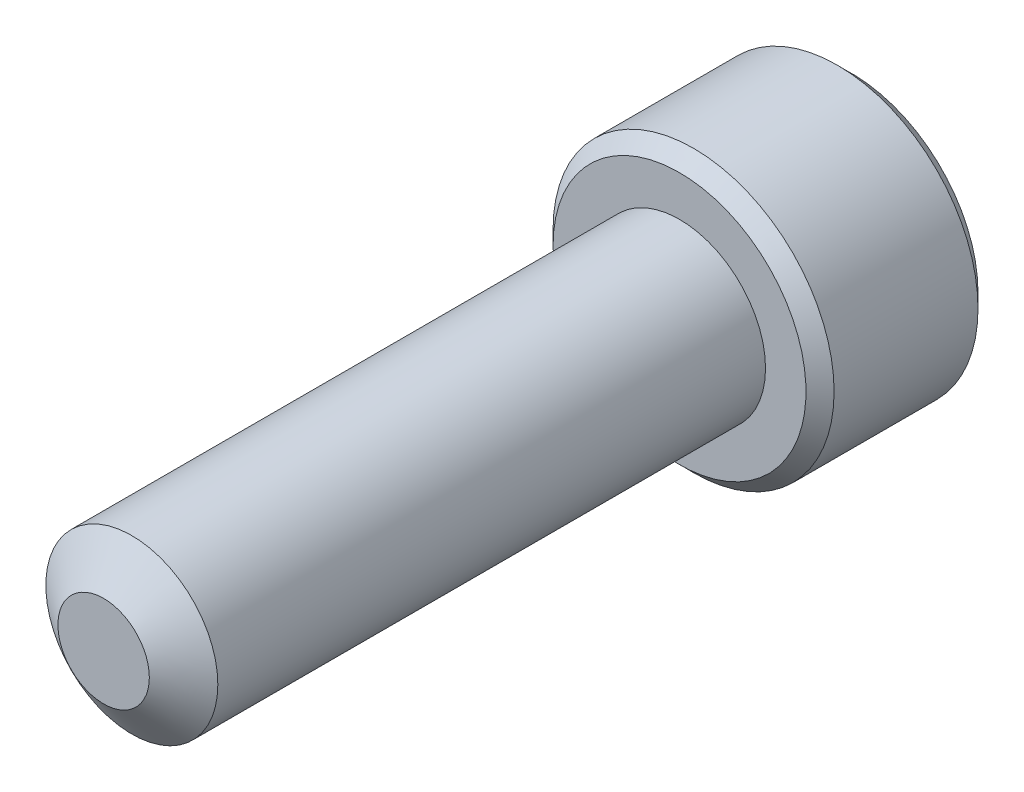
SolidWorks part; units mm, degrees
material "6061 Alloy"
ref_plane "Front Plane" through (0, 0, 0) normal (0, 0, 1) x (1, 0, 0)
ref_plane "Top Plane" through (0, 0, 0) normal (0, 1, 0) x (1, 0, 0)
ref_plane "Right Plane" through (0, 0, 0) normal (1, 0, 0) x (0, 0, -1)
sketch "Sketch1" plane through (0, 0, 0) normal (0, 0, 1) x (1, 0, 0)
  circle A0 centre (0, 0) radius 1.4224
  dimension "OD" = 2.8448
extrude "Extrude1" add sketch "Sketch1" against normal blind 9.525
sketch "Sketch2" plane through (0, 0, 0) normal (0, 0, 1) x (1, 0, 0)
  circle A0 centre (0, 0) radius 1.4224 construction
  circle A1 centre (0, 0) radius 1.4224
curve "Helix/Spiral1" [suppressed] pitch 0.635 height 10.16 turns 16 parameters "pitch"=0.635
sketch "Sketch3" plane through (0, 0, 0) normal (1, 0, 0) x (0, 0, -1)
  line L0 (-0.5556, 1.4224) -> (-0.3175, 1.01)
  line L1 (-0.3175, 1.01) -> (-0.2381, 1.01)
  line L2 (-0.2381, 1.01) -> (0, 1.4224)
  line L3 (-0.5556, 1.4224) -> (0, 1.4224)
  line L4 (-0.2778, 1.4224) -> (-0.2778, 1.01) construction
  line L5 (-0.4366, 1.2162) -> (-0.1191, 1.2162) construction
  line L6 (0, 1.4224) -> (0, -1.4224) construction
  dimension "D1" = 0.0794
  dimension "D2" = 0.3175
  dimension "D3" = 60
sweep "Cut-Sweep1" [suppressed] cut profiles "Sketch3" path "Helix/Spiral1"
sketch "Sketch4" plane through (0, 0, 0) normal (1, 0, 0) x (0, 0, -1)
  line L0 (0.4666, 1.4224) -> (0, 0.756)
  line L1 (0, 0.756) -> (0, 1.4224)
  line L2 (0.4666, 1.4224) -> (0, 1.4224)
  line L3 (-0.5556, 1.4224) -> (0, 1.4224) construction
  line L4 (0, 0) -> (7.0209, 0) construction
  dimension "D1" = 55
  dimension "D2" = 0.254
revolve "Cut-Revolve1" cut sketch "Sketch4" angle 360 about L4
sketch "Sketch6" plane through (0, 0, -9.525) normal (0, 0, -1) x (-1, 0, 0)
  circle A0 centre (0, 0) radius 2.3241
  dimension "head dia" = 4.6482
extrude "Extrude2" add sketch "Sketch6" along normal blind 2.8448
sketch "Sketch7" plane through (0, 0, -12.3698) normal (0, 0, -1) x (-1, 0, 0)
  line L1 (0, 1.3748) -> (-1.1906, 0.6874)
  line L2 (-1.1906, 0.6874) -> (-1.1906, -0.6874)
  line L3 (-1.1906, -0.6874) -> (0, -1.3748)
  line L4 (0, -1.3748) -> (1.1906, -0.6874)
  line L5 (1.1906, -0.6874) -> (1.1906, 0.6874)
  line L6 (1.1906, 0.6874) -> (0, 1.3748)
  circle A0 centre (0, 0) radius 1.1906 construction
  dimension "hex dia" = 2.3813
extrude "Cut-Extrude1" cut sketch "Sketch7" against normal blind 1.7859
sketch "Sketch8" plane through (0, 0, -12.3698) normal (0, 0, -1) x (-1, 0, 0)
  circle A0 centre (0, 0) radius 1.3748
extrude "Cut-Extrude2" cut sketch "Sketch8" against normal through all draft 45
chamfer "Chamfer1" distance 0.2324 angle 45 2 edges at (-2.3241, 0, -12.3698) (-2.3241, 0, -9.525)
sketch "Sketch10" plane through (0, 0, -9.525) normal (0, 0, 1) x (1, 0, 0)
  circle A1 centre (0, 0) radius 1.4224
  circle A2 centre (0, 0) radius 1.4224
  dimension "D1" = 0
ref_plane "Plane1" through (0, 0, 0) normal (0, 0, 1) x (1, 0, 0)
extrude "partial thread" [suppressed] add sketch "Sketch10" along normal up to surface (12.7 mm away) separate body up to plane "Plane1"
chamfer "Chamfer2" [suppressed] distance 0.0569 angle 45
combine bodies "Combine1" [suppressed] operation type add bodies to combine 107 108
sketch "Sketch9" [suppressed] plane through (0, 0, 0) normal (1, 0, 0) x (0, 0, -1)
  line L0 (0, 1.4224) -> (0, -1.4224) construction
  line L1 (1.5875, 1.4224) -> (1.5875, -1.4224) construction
  dimension "D1" = 1.5875
equation "\"D3@Helix/Spiral1\" = \"screw length@Extrude1\"+\"pitch@Helix/Spiral1\""
equation "\"D1@Sketch3\" = \"pitch@Helix/Spiral1\"*.125"
equation "\"D2@Sketch3\" = \"pitch@Helix/Spiral1\"*.5"
equation "\"D1@Cut-Extrude1\" = \"hex dia@Sketch7\"*.75"
equation "\"D1@Chamfer1\" = \"head dia@Sketch6\"*.05"
equation "\"D1@Sketch9\" = \"pitch@Helix/Spiral1\"*2.5"
equation "\"D1@Chamfer2\"=\"OD@Sketch1\"*.02"
